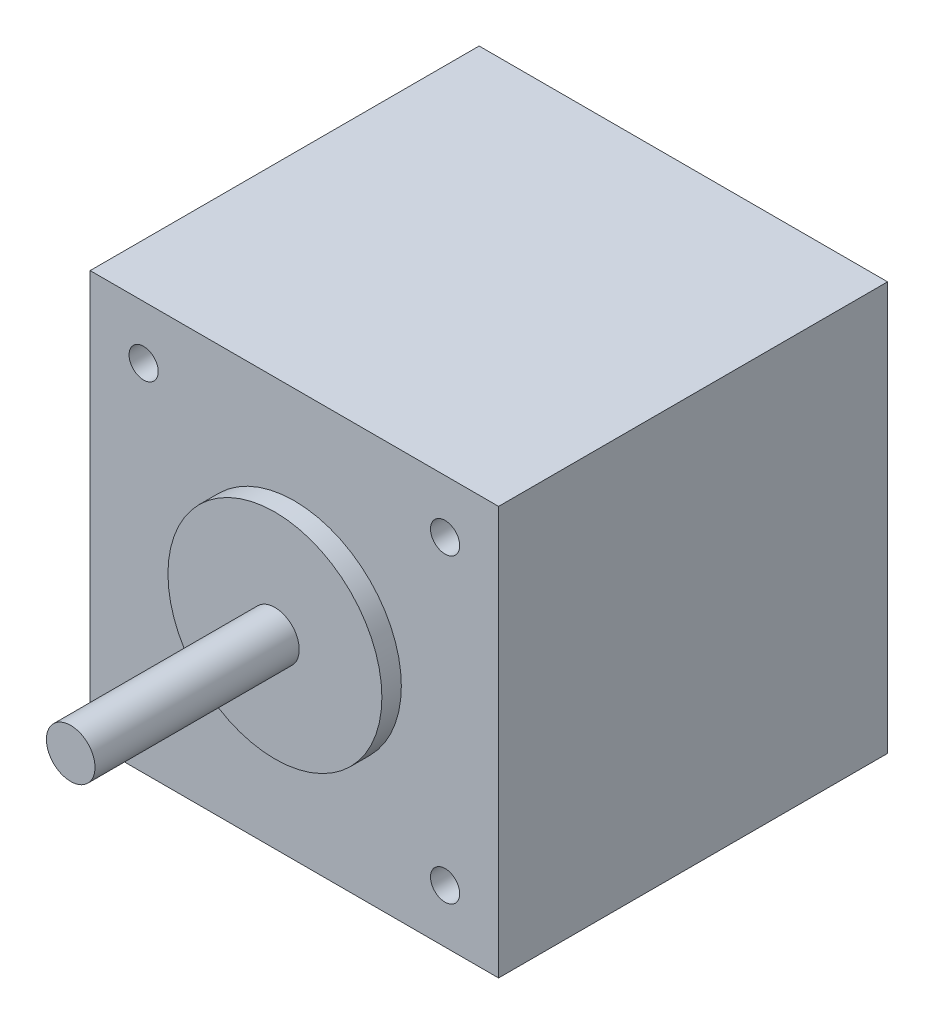
SolidWorks part; units mm, degrees
ref_plane "Спереди" through (0, 0, 0) normal (0, 0, 1) x (1, 0, 0)
ref_plane "Сверху" through (0, 0, 0) normal (0, 1, 0) x (1, 0, 0)
ref_plane "Справа" through (0, 0, 0) normal (1, 0, 0) x (0, 0, -1)
other "Configuration Table"
sketch "Эскиз1" plane through (0, 0, 0) normal (0, 0, 1) x (1, 0, 0)
  line L1 (-21, -21) -> (21, -21)
  line L2 (-21, -21) -> (-21, 21)
  line L3 (-21, 21) -> (21, 21)
  line L4 (21, -21) -> (21, 21)
  line L5 (-21, -21) -> (21, 21) construction
  line L6 (-21, 21) -> (21, -21) construction
  point P0 (0, 0)
  dimension "D1" = 42
  dimension "D2" = 42
extrude "Корпус" add sketch "Эскиз1" along normal blind 40
sketch "Эскиз2" plane through (0, 0, 0) normal (0, 0, 1) x (1, 0, 0)
  circle A0 centre (0, 0) radius 2.5
extrude "Вал_ПРЕДВ" add sketch "Эскиз2" along normal blind 63
sketch "Эскиз3" plane through (0, 0, 0) normal (0, 0, 1) x (1, 0, 0)
  circle A0 centre (0, 0) radius 11
  dimension "D1" = 22
extrude "Буртик_ПРЕДВ" add sketch "Эскиз3" along normal blind 42
sketch "Эскиз4" plane through (0, 0, 0) normal (0, 0, 1) x (1, 0, 0)
  circle A0 centre (-15.5, -15.5) radius 1.5
  circle A1 centre (-15.5, 15.5) radius 1.5
  circle A2 centre (15.5, -15.5) radius 1.5
  circle A3 centre (15.5, 15.5) radius 1.5
  dimension "D1" = 3
  dimension "D2" = 3
  dimension "D3" = 3
  dimension "D4" = 3
extrude "Крепеж_М3_ПРЕДВ" cut sketch "Эскиз4" against normal blind 4.5 from offset 40
equation "\"Мотор X ширина корпуса\"= 42.3"
equation "\"Мотор X высота корпуса\"= 42.3"
equation "\"Мотор X длина корпуса\"= 40"
equation "\"Мотор X вылет вала\"= 19.8"
equation "\"Мотор Y ширина корпуса\"= 42.3"
equation "\"Мотор Y высота корпуса\"= 42.3"
equation "\"Мотор Y длина корпуса\"= 48"
equation "\"Мотор Y вылет вала\"= 30"
equation "\"Мотор Z ширина корпуса\"= 42"
equation "\"Мотор Z высота корпуса\"= 42"
equation "\"Мотор Z длина корпуса\"= 40"
equation "\"Мотор Z вылет вала\"= 23"
equation "\"Мотор диаметр вала ПРЕДВ\"= 5"
equation "\"Мотор шаг крепления ПРЕДВ\"= 31"
equation "\"Мотор диаметр отверстий ПРЕДВ\"= 3"
equation "\"Мотор глубина отверстий ПРЕДВ\"= 4.5"
equation "\"Мотор диаметр буртика ПРЕДВ\"= 22"
equation "\"Мотор высота буртика ПРЕДВ\"= 2"
equation "\"Мотор диаметр шкива ПРЕДВ\"= 16"
equation "\"Мотор длина шкива ПРЕДВ\"= 12"
equation "\"Мотор отступ шкива ПРЕДВ\"= 5"
equation "\"Мотор X шаг градусов\"= 1.8"
equation "\"Мотор X ток А\"= 1.5"
equation "\"Мотор X сопротивление Ом\"= 1.3"
equation "\"Мотор X индуктивность мГн\"= 2"
equation "\"Мотор Y шаг градусов\"= 1.8"
equation "\"Мотор Y ток А\"= 2.2"
equation "\"Мотор Y сопротивление Ом\"= 0.9"
equation "\"Мотор Y индуктивность мГн\"= 2"
equation "\"Мотор Z шаг градусов\"= 1.8"
equation "\"Мотор Z ток А\"= 1"
equation "\"Мотор Z сопротивление Ом\"= 4"
equation "\"Мотор Z индуктивность мГн\"= 8"
equation "\"Мотор Y диаметр ротора\"= 25.78"
equation "\"D1@Эскиз1\" = \"Мотор Z ширина корпуса\""
equation "\"D2@Эскиз1\" = \"Мотор Z высота корпуса\""
equation "\"D1@Корпус\" = \"Мотор Z длина корпуса\""
equation "\"D1@Эскиз2\" = \"Мотор диаметр вала ПРЕДВ\""
equation "\"D1@Вал_ПРЕДВ\" = \"Мотор Z длина корпуса\" + \"Мотор Z вылет вала\""
equation "\"D1@Эскиз3\" = \"Мотор диаметр буртика ПРЕДВ\""
equation "\"D1@Буртик_ПРЕДВ\" = \"Мотор Z длина корпуса\" + \"Мотор высота буртика ПРЕДВ\""
equation "\"D1@Эскиз4\" = \"Мотор диаметр отверстий ПРЕДВ\""
equation "\"D2@Эскиз4\" = \"Мотор диаметр отверстий ПРЕДВ\""
equation "\"D3@Эскиз4\" = \"Мотор диаметр отверстий ПРЕДВ\""
equation "\"D4@Эскиз4\" = \"Мотор диаметр отверстий ПРЕДВ\""
equation "\"D1@Крепеж_М3_ПРЕДВ\" = \"Мотор глубина отверстий ПРЕДВ\""
equation "\"D19@Крепеж_М3_ПРЕДВ\" = \"Мотор Z длина корпуса\""
equation "\"Ширина груза\"= 420"
equation "\"Глубина груза\"= 490"
equation "\"Высота груза\"= 297"
equation "\"Ширина ячейки\"= \"Ширина груза\" + 10"
equation "\"Глубина ячейки\"= \"Глубина груза\" + 10"
equation "\"Высота ячейки\"= \"Высота груза\" + 10 + 13"
equation "\"Колво ячеек ширина\"= 2"
equation "\"Колво ячеек высота\"= 2"
equation "\"Толщина стенки\" = 6"
equation "\"Крепление дверцы\"= 5 "
equation "\"Ширина рейки\"= \"Толщина шестерни\""
equation "\"Высота рейки\"= 20"
equation "\"Высота пола\"= \"Толщина стенки\" * 2"
equation "\"Колво полозьев\"= 5"
equation "\"Отступ рейки\"= 20"
equation "\"Глубина каретки\"= \"Глубина ячейки\" + 30 + \"Мотор Y высота корпуса\" + 20"
equation "\"Отступ шпильки\"= 26"
equation "\"Диаметр шпильки\"= 5"
equation "\"Длинна шпильки\"= ( \"Высота ячейки\" + \"Толщина стенки\" + \"Высота пола\" ) * \"Колво ячеек высота\" + ( \"Толщина стенки\" + \"Отступ рейки\" ) * 2 "
equation "\"Ширина пластины\"= 50  "
equation "\"Высота зона выгрузки\"= \"Высота ячейки\" * 2 + \"Толщина стенки\" * 2"
equation "\"Колво выгрузки\"= 1"
equation "\"Отступ крепления мотора фиксации\" = 30"
equation "\"Диаметр оси\"= 10"
equation "\"Диаметр ролика\"= 20"
equation "\"Колво роликов\"= 10"
equation "\"Шаг роликов\"= \"Диаметр ролика\" + 20"
equation "\"Ширина ячейки выгрузки\"= \"Ширина ячейки\" + \"Толщина стенки\" + \"Отступ крепления мотора фиксации\"*2"
equation "\"Длинна рейки\"= ( \"Ширина ячейки\" + \"Толщина стенки\" + \"Крепление дверцы\" ) * \"Колво ячеек ширина\" + \"Ширина ячейки выгрузки\" * \"Колво выгрузки\" + \"Толщина стенки\""
